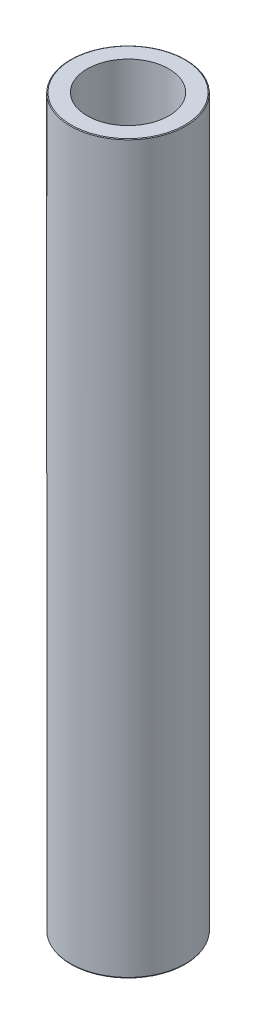
SolidWorks part; units mm, degrees
ref_plane "Front Plane" through (0, 0, 0) normal (0, 0, 1) x (1, 0, 0)
ref_plane "Top Plane" through (0, 0, 0) normal (0, 1, 0) x (1, 0, 0)
ref_plane "Right Plane" through (0, 0, 0) normal (1, 0, 0) x (0, 0, -1)
sketch "Sketch1" plane through (0, 0, 0) normal (0, 1, 0) x (1, 0, 0)
  circle A0 centre (0, 0) radius 47.5
  dimension "SHAFT_OD" = 95
extrude "Boss-Extrude1" add sketch "Sketch1" along normal blind 600
sketch "Sketch2" plane through (0, 0, 0) normal (0, 1, 0) x (1, 0, 0)
  circle A0 centre (0, 0) radius 33.67
  dimension "BORE_D" = 67.3401
extrude "Cut-Extrude1" cut sketch "Sketch2" along normal through all
chamfer "Chamfer1" distance 0.4092 angle 60 2 edges at (0, 600, 47.5) (0, 0, 47.5) first distance on face at (0, 600, 47.5) first distance on face at (0, 0, 33.67)
